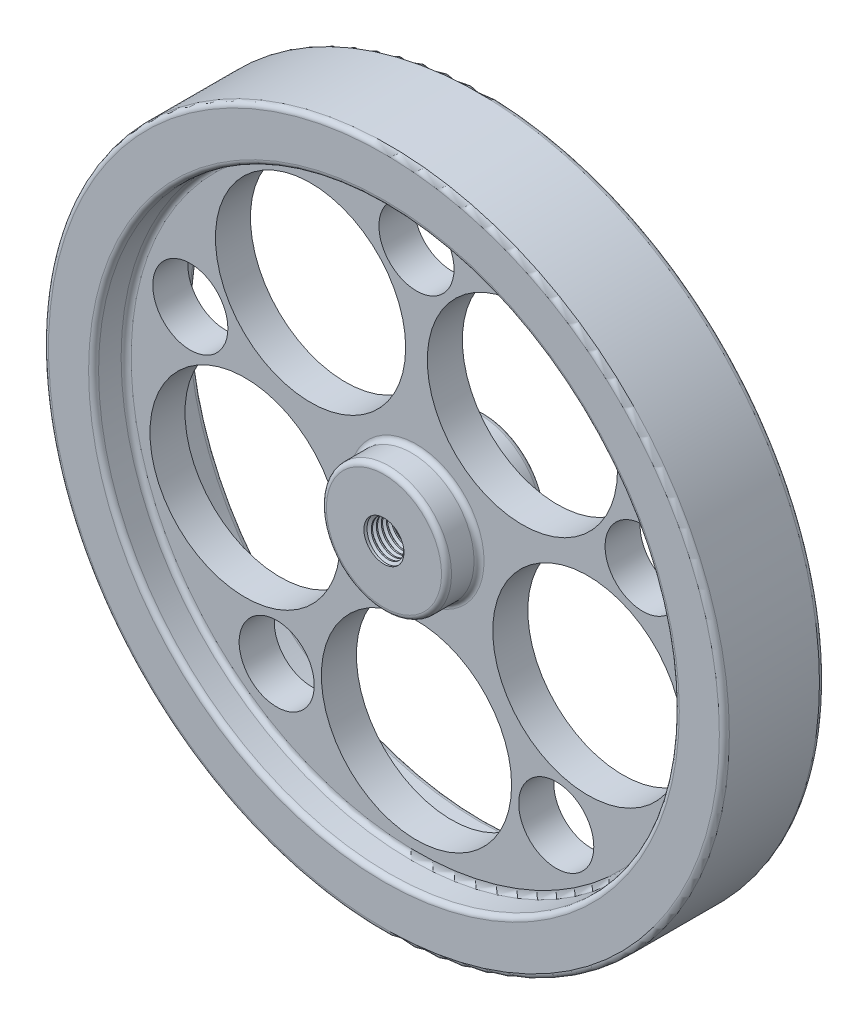
SolidWorks part; units mm, degrees
ref_plane "Front Plane" through (0, 0, 0) normal (0, 0, 1) x (1, 0, 0)
ref_plane "Top Plane" through (0, 0, 0) normal (0, 1, 0) x (1, 0, 0)
ref_plane "Right Plane" through (0, 0, 0) normal (1, 0, 0) x (0, 0, -1)
sketch "Sketch1" plane through (0, 0, 0) normal (0, 0, 1) x (1, 0, 0)
  circle A0 centre (0, 0) radius 68
  dimension "D1" = 136
extrude "Boss-Extrude1" add sketch "Sketch1" along normal blind 7
sketch "Sketch2" plane through (0, 0, 7) normal (0, 0, 1) x (1, 0, 0)
  circle A0 centre (0, 0) radius 68
  circle A1 centre (0, 0) radius 58
  dimension "D1" = 116
extrude "Boss-Extrude2" add sketch "Sketch2" along normal blind 6.5
sketch "Sketch3" plane through (0, 0, 0) normal (0, 0, -1) x (-1, 0, 0)
  circle A0 centre (0, 0) radius 68
  circle A1 centre (0, 0) radius 58
  dimension "D1" = 116
extrude "Boss-Extrude3" add sketch "Sketch3" along normal blind 6.5
sketch "Sketch4" plane through (0, 0, 0) normal (0, 0, -1) x (-1, 0, 0)
  circle A0 centre (0, 0) radius 12.5
  dimension "D1" = 25
extrude "Boss-Extrude4" add sketch "Sketch4" along normal up to surface (6.5 mm away) up to face at (-68, 0, -6.5)
sketch "Sketch5" plane through (0, 0, 7) normal (0, 0, 1) x (1, 0, 0)
  circle A0 centre (0, 0) radius 12.5
  dimension "D1" = 25
extrude "Boss-Extrude5" add sketch "Sketch5" along normal up to surface (6.5 mm away) up to face at (68, 0, 13.5)
sketch "Sketch6" plane through (0, 0, 13.5) normal (0, 0, 1) x (1, 0, 0)
  circle A0 centre (0, 0) radius 4
  dimension "D1" = 8
extrude "Cut-Extrude1" cut sketch "Sketch6" against normal through all
sketch "Sketch7" plane through (0, 0, 7) normal (0, 0, 1) x (1, 0, 0)
  circle A0 centre (0, 0) radius 47.5 construction
  circle A1 centre (0, 47.5) radius 7.5
  circle A2 centre (45.1752, 14.6783) radius 7.5
  circle A3 centre (27.9198, -38.4283) radius 7.5
  circle A4 centre (-27.9198, -38.4283) radius 7.5
  circle A5 centre (-45.1752, 14.6783) radius 7.5
  circle A6 centre (0, 0) radius 36 construction
  circle A8 centre (0, -36) radius 19
  circle A9 centre (0, 0) radius 55 construction
  circle A10 centre (-34.238, -11.1246) radius 19
  circle A11 centre (-21.1603, 29.1246) radius 19
  circle A12 centre (21.1603, 29.1246) radius 19
  circle A13 centre (34.238, -11.1246) radius 19
  point P16 (0, 0)
  point P29 (0, 0)
  dimension "D1" = 95
  dimension "D2" = 15
  dimension "D4" = 38
  dimension "D5" = 5
  dimension "D3" = 5
extrude "Cut-Extrude2" cut sketch "Sketch7" against normal through all
fillet "Fillet1" radius 1 8 edges at (-12.5, 0, -6.5) (12.5, 0, 0) (-58, 0, -6.5) (-68, 0, -6.5) (12.5, 0, 13.5) (12.5, 0, 7) (58, 0, 13.5) (68, 0, 13.5)
fillet "Fillet2" radius 1 2 edges at (-58, 0, 0) (58, 0, 7)
thread "Thread1" pitch 1 method extrude profile "Thread Profile1" start angle 0, offset 0, length 19, pitch 1, diameter 8
ref_plane "Plane1" through (4, 0, -6.5) normal (0, -1, 0) x (1, 0, 0)
sketch "Thread Profile1" plane through (4, 0, -6.5) normal (0, -1, 0) x (1, 0, 0)
  line L0 (0, 0) -> (0, 1) construction
  line L11 (0, 0) -> (0, 0.875)
  line L12 (0, 0.875) -> (-0.5413, 0.5625)
  line L13 (-0.5413, 0.5625) -> (-0.5413, 0.3125)
  line L15 (-0.5413, 0.3125) -> (0, 0)
  line L17 (-0.5413, 0.4375) -> (0, 0.4375) construction
  point P2 (0, 0)
  dimension "Pitch" = 1
  dimension "Profile_Angle" = 60
  dimension "Profile_Land" = 0.25
  dimension "Profile_Height" = 0.5413
